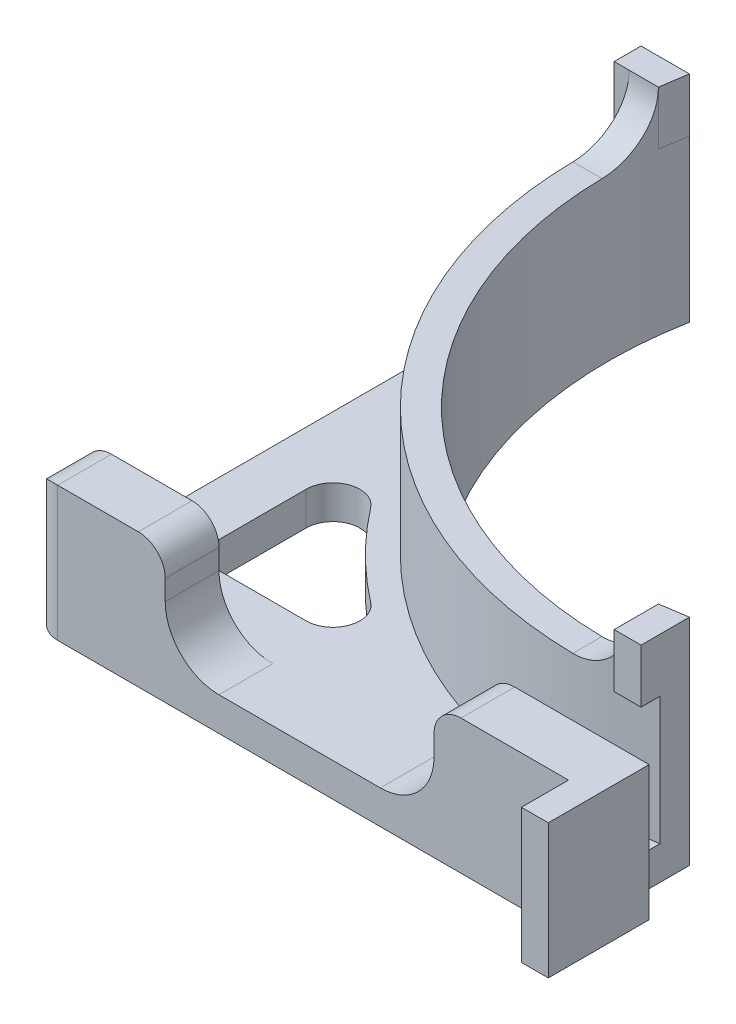
SolidWorks part; units mm, degrees
ref_plane "Front Plane" through (0, 0, 0) normal (0, 0, 1) x (1, 0, 0)
ref_plane "Top Plane" through (0, 0, 0) normal (0, 1, 0) x (1, 0, 0)
ref_plane "Right Plane" through (0, 0, 0) normal (1, 0, 0) x (0, 0, -1)
sketch "Sketch1" plane through (0, 0, 0) normal (0, 1, 0) x (1, 0, 0)
  line L7 (2.54, 2.54) -> (2.54, 12.3466)
  line L11 (0, 0) -> (25.4, 0)
  line L12 (0, 0) -> (0, 25.4)
  line L13 (0, 25.4) -> (3.175, 25.4)
  line L14 (25.4, 0) -> (25.4, 3.175)
  line L15 (2.54, 12.3466) -> (2.54, 12.3466)
  line L16 (12.3466, 2.54) -> (12.3466, 2.54)
  line L17 (2.54, 2.54) -> (12.3466, 2.54)
  arc A1 (3.175, 25.4) -> (25.4, 3.175) centre (21.9009, 21.9009) ccw
  arc A2 (2.54, 12.3466) -> (12.3466, 2.54) centre (21.9009, 21.9009) ccw
  dimension "D1" = 25.4
  dimension "D2" = 38.1
  dimension "D3" = 3.175
  dimension "D4" = 3.175
  dimension "D5" = 2.54
extrude "Boss-Extrude1" add sketch "Sketch1" along normal blind 7.62
sketch "Sketch2" plane through (0, 7.62, 0) normal (0, 1, 0) x (1, 0, 0)
  circle A0 centre (21.9009, 21.9009) radius 19.05 construction
  circle A1 centre (21.9009, 21.9009) radius 20.4239
  circle A2 centre (21.9009, 21.9009) radius 33.2852
extrude "Cut-Extrude1" cut sketch "Sketch2" against normal blind 6.0325
sketch "Sketch3" plane through (0, 0, 0) normal (0, 0, 1) x (1, 0, 0)
  line L0 (0, 1.5875) -> (25.4, 1.5875) construction
  line L2 (0, 0) -> (0, 6.35)
  line L3 (0, 6.35) -> (6.35, 6.35)
  line L4 (6.35, 1.5875) -> (6.35, 6.35)
  line L6 (25.4, 0) -> (25.4, 6.35)
  line L7 (25.4, 6.35) -> (19.05, 6.35)
  line L8 (19.05, 1.5875) -> (19.05, 6.35)
  line L11 (6.35, 1.5875) -> (19.05, 1.5875)
  line L14 (0, 0) -> (25.4, 0)
  dimension "D1" = 6.35
  dimension "D2" = 12.7
extrude "Boss-Extrude2" add sketch "Sketch3" along normal blind 2.54
sketch "Sketch4" plane through (0, 7.62, 0) normal (0, 1, 0) x (1, 0, 0)
  line L0 (3.175, 25.4) -> (0.8895, 25.4)
  line L1 (1.779, 25.4) -> (0, 25.4) construction
  line L2 (0.8895, 25.4) -> (0.8895, 24.13)
  line L3 (0.8895, 24.13) -> (2.9818, 24.13)
  line L4 (2.9818, 24.13) -> (3.175, 25.4)
  line L5 (25.4, 3.175) -> (25.4, 0.8895)
  line L6 (25.4, 0) -> (25.4, 1.779) construction
  line L7 (25.4, 0.8895) -> (24.13, 0.8895)
  line L8 (24.13, 0.8895) -> (24.13, 2.9818)
  line L9 (24.13, 2.9818) -> (25.4, 3.175)
  arc A0 (3.175, 25.4) -> (25.4, 3.175) centre (21.9009, 21.9009) ccw construction
  point P19 (25.4, 0.8895)
  dimension "D1" = 1.27
  dimension "D2" = 1.27
extrude "Boss-Extrude3" add sketch "Sketch4" along normal blind 2.54
sketch "Sketch5" plane through (25.4, 0, 0) normal (1, 0, 0) x (0, 0, -1)
  line L0 (-2.54, 6.35) -> (0, 6.35) construction
  line L1 (0, 0) -> (-4.7625, 0)
  line L2 (0, 0) -> (0, 6.35)
  line L3 (0, 6.35) -> (-4.7625, 6.35)
  line L4 (-4.7625, 0) -> (-4.7625, 6.35)
  dimension "D1" = 4.7625
extrude "Boss-Extrude4" add sketch "Sketch5" along normal blind 1.27
fillet "Fillet1" radius 2.54 4 edges at (19.05, 1.5875, 1.27) (6.35, 1.5875, 1.27) (2.2904, 7.62, -24.13) (24.13, 7.62, -2.2904)
fillet "Fillet2" radius 1.27 8 edges at (2.54, 0.7937, -12.3466) (12.3466, 0.7937, -2.54) (2.54, 0.7938, -2.54) (0, 0.7937, -25.4) (0, 3.175, 2.54) (19.05, 6.35, 1.27) (6.35, 6.35, 1.27) (0, 6.35, 1.27)
